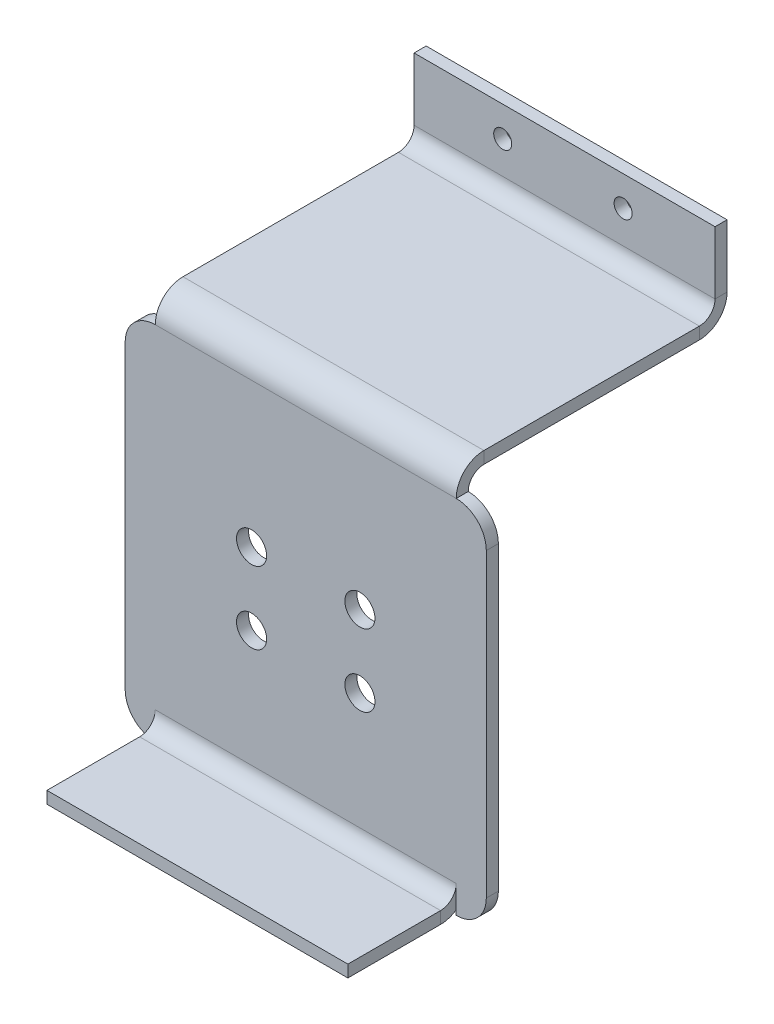
SolidWorks part; units mm, degrees
note: The reader was unsure of these and kept them because the rebuilt part matched: flange length of "Edge-Flange1", "Edge-Flange2", "Edge-Flange3".
material "Alumina"
ref_plane "Front Plane" through (0, 0, 0) normal (0, 0, 1) x (1, 0, 0)
ref_plane "Top Plane" through (0, 0, 0) normal (0, 1, 0) x (1, 0, 0)
ref_plane "Right Plane" through (0, 0, 0) normal (1, 0, 0) x (0, 0, -1)
sketch "Sketch1" plane through (0, 0, 0) normal (0, 0, 1) x (1, 0, 0)
  line L0 (25.2729, 31.228) -> (-24.7271, 31.228)
  line L1 (-29.7271, 26.228) -> (-29.7271, -23.772)
  line L2 (-24.7271, -28.772) -> (25.2729, -28.772)
  line L3 (30.2729, -23.772) -> (30.2729, 26.228)
  arc A0 (-24.7271, 31.228) -> (-29.7271, 26.228) centre (-24.7271, 26.228) ccw
  arc A1 (-29.7271, -23.772) -> (-24.7271, -28.772) centre (-24.7271, -23.772) ccw
  arc A2 (25.2729, -28.772) -> (30.2729, -23.772) centre (25.2729, -23.772) ccw
  arc A3 (30.2729, 26.228) -> (25.2729, 31.228) centre (25.2729, 26.228) ccw
  arc A13 (11.7728, -4.772) -> (9.2729, -2.2721) centre (9.2729, -4.772) ccw
  arc A14 (-8.7271, -2.2721) -> (-11.227, -4.772) centre (-8.7271, -4.772) ccw
  arc A15 (-11.227, -4.772) -> (-6.2272, -4.772) centre (-8.7271, -4.772) ccw
  arc A16 (-6.2272, -4.772) -> (-8.7271, -2.2721) centre (-8.7271, -4.772) ccw
  arc A17 (9.2729, -2.2721) -> (6.773, -4.772) centre (9.2729, -4.772) ccw
  arc A18 (6.773, -4.772) -> (11.7728, -4.772) centre (9.2729, -4.772) ccw
  arc A19 (6.773, 7.228) -> (11.7728, 7.228) centre (9.2729, 7.228) ccw
  arc A20 (9.2729, 9.7279) -> (6.773, 7.228) centre (9.2729, 7.228) ccw
  arc A21 (11.7728, 7.228) -> (9.2729, 9.7279) centre (9.2729, 7.228) ccw
  arc A22 (-8.7271, 9.7279) -> (-11.227, 7.228) centre (-8.7271, 7.228) ccw
  arc A23 (-6.2272, 7.228) -> (-8.7271, 9.7279) centre (-8.7271, 7.228) ccw
  arc A24 (-11.227, 7.228) -> (-6.2272, 7.228) centre (-8.7271, 7.228) ccw
  dimension "D1" = 5
  dimension "D2" = 9.2729
  dimension "D3" = 2.4999
  dimension "D8" = 8.7271
  dimension "D4" = 9.7279
  dimension "D5" = 31.228
  dimension "D6" = 2.2721
  dimension "D7" = 28.772
  dimension "D11" = 25.2729
base flange "Base-Flange2" sketch "Sketch1" thickness 2 reverse thickness direction no parameters "D1"=2.6
edge flange "Edge-Flange1" sketch "Sketch14" flange angle 90 flange length 45 flange position bend outside bend radius 2.6 thickness 2 parameters "D6"=10
sketch "Sketch14" plane through (0, 31.228, -2) normal (0, 1, 0) x (1, 0, 0)
  line L0 (25.2729, 0) -> (-24.7271, 0) construction
  line L1 (25.2729, 0) -> (-24.7271, 0)
  line L2 (-24.7271, 0) -> (-24.7271, 43)
  line L3 (-24.7271, 43) -> (25.2729, 43)
  line L4 (25.2729, 43) -> (25.2729, 0)
bend "EdgeBend1" bend radius 2.6 bend angle 90 parameters "D5"=1
edge flange "Edge-Flange2" sketch "Sketch17" flange angle 90 flange length 15 flange position material inside bend radius 2.6 thickness 2 parameters "D6"=10
sketch "Sketch17" plane through (0, 35.828, -45) normal (0, 0, -1) x (-1, 0, 0)
  line L0 (-25.2729, 0) -> (24.7271, 0) construction
  line L1 (-25.2729, 0) -> (24.7271, 0)
  line L2 (-25.2729, 0) -> (-25.2729, 13)
  line L3 (-25.2729, 13) -> (24.7271, 13)
  line L4 (24.7271, 13) -> (24.7271, 0)
bend "EdgeBend2" bend radius 2.6 bend angle 90 parameters "D5"=2
sketch "Sketch18" plane through (0, 0, -45) normal (0, 0, -1) x (-1, 0, 0)
  line L0 (0, -2.5637) -> (0, 58.1921) construction
  line L1 (24.7271, 48.828) -> (-25.2729, 48.828) construction
  circle A0 centre (-10, 43.828) radius 1.5
  circle A1 centre (10, 43.828) radius 1.5
  dimension "D4" = 3
  dimension "D1" = 10
  dimension "D2" = 10
  dimension "D3" = 5
extrude "Cut-Extrude1" cut sketch "Sketch18" against normal blind 10
edge flange "Edge-Flange3" sketch "Sketch21" flange angle 90 flange length 20 flange position material inside bend radius 2.6 thickness 2 parameters "D6"=10
sketch "Sketch21" plane through (0, -28.772, 0) normal (0, -1, 0) x (1, 0, 0)
  line L2 (-24.7271, 0) -> (-24.7271, 18)
  line L3 (-24.7271, 18) -> (25.2729, 18)
  line L4 (25.2729, 18) -> (25.2729, 0)
  line L7 (-24.7271, 0) -> (25.2729, 0) construction
  line L8 (-24.7271, 0) -> (25.2729, 0)
bend "EdgeBend3" bend radius 2.6 bend angle 90 parameters "D5"=3
sketch "Bend-Lines3" [suppressed] plane through (0, 0, 0) normal (0, 1, 0) x (1, 0, 0)
sketch "Bounding-Box3" [suppressed] plane through (0, 0, 0) normal (0, 1, 0) x (1, 0, 0)
sheet metal parameters "Sheet-Metal2" thickness 2 parameters "D1"=2.6
flat pattern "Flat-Pattern2" [suppressed]
sketch "Bend-Lines4" plane through (0, 0, 0) normal (0, 1, 0) x (1, 0, 0)
sketch3d "Bounding-Box4" [suppressed]
  line L0 (-5, -55, 0) -> (-5, 5, 0) construction
  line L1 (55, -55, 0) -> (55, 5, 0) construction
  line L2 (-5, -55, 0) -> (55, -55, 0) construction
  line L3 (-5, 5, 0) -> (55, 5, 0) construction
sheet metal parameters "Sheet-Metal3" thickness 2 parameters "D1"=2.6
flat pattern "Flat-Pattern2"
sketch "Bend-Lines4" plane through (0, 0, 0) normal (0, 0, 1) x (1, 0, 0)
  line L0 (25.2729, 34.0554) -> (-24.7271, 34.0554) construction
  line L1 (25.2729, 34.0554) -> (-24.7271, 34.0554) construction
sketch3d "Bounding-Box4" [suppressed]
  line L0 (5, -55, 0) -> (5, 51.0549, 0) construction
  line L1 (-55, -55, 0) -> (-55, 51.0549, 0) construction
  line L2 (5, -55, 0) -> (-55, -55, 0) construction
  line L3 (5, 51.0549, 0) -> (-55, 51.0549, 0) construction
bend of the flat pattern "Flatten-<EdgeBend1>1"
sheet metal parameters "Sheet-Metal4" thickness 2 parameters "D1"=2.6
flat pattern "Flat-Pattern2"
sketch "Bend-Lines4" plane through (0, 0, 0) normal (0, 0, 1) x (1, 0, 0)
  line L0 (25.2729, 34.0554) -> (-24.7271, 34.0554) construction
  line L1 (25.2729, 34.0554) -> (-24.7271, 34.0554) construction
  line L2 (25.2729, 75.5103) -> (-24.7271, 75.5103) construction
  line L3 (25.2729, 75.5103) -> (-24.7271, 75.5103) construction
sketch3d "Bounding-Box4" [suppressed]
  line L0 (5, -55, 0) -> (5, 62.5097, 0) construction
  line L1 (-55, -55, 0) -> (-55, 62.5097, 0) construction
  line L2 (5, -55, 0) -> (-55, -55, 0) construction
  line L3 (5, 62.5097, 0) -> (-55, 62.5097, 0) construction
bend of the flat pattern "Flatten-<EdgeBend1>1"
bend of the flat pattern "Flatten-<EdgeBend2>1"
sheet metal parameters "Sheet-Metal5" thickness 2 parameters "D1"=2.6
flat pattern "Flat-Pattern2"
sketch "Bend-Lines4" plane through (0, 0, 0) normal (0, 0, 1) x (1, 0, 0)
  line L0 (25.2729, 34.0554) -> (-24.7271, 34.0554) construction
  line L1 (25.2729, 34.0554) -> (-24.7271, 34.0554) construction
  line L2 (25.2729, 75.5103) -> (-24.7271, 75.5103) construction
  line L3 (25.2729, 75.5103) -> (-24.7271, 75.5103) construction
sketch3d "Bounding-Box4" [suppressed]
  line L0 (5, -55, 0) -> (5, 62.5097, 0) construction
  line L1 (-55, -55, 0) -> (-55, 62.5097, 0) construction
  line L2 (5, -55, 0) -> (-55, -55, 0) construction
  line L3 (5, 62.5097, 0) -> (-55, 62.5097, 0) construction
bend of the flat pattern "Flatten-<EdgeBend1>1"
bend of the flat pattern "Flatten-<EdgeBend2>1"
sheet metal parameters "Sheet-Metal6" thickness 2 parameters "D1"=2.6
flat pattern "Flat-Pattern2"
sketch "Bend-Lines4" plane through (0, 0, 0) normal (0, 0, 1) x (1, 0, 0)
  line L0 (25.2729, 34.0554) -> (-24.7271, 34.0554) construction
  line L1 (25.2729, 34.0554) -> (-24.7271, 34.0554) construction
  line L2 (25.2729, 75.5103) -> (-24.7271, 75.5103) construction
  line L3 (25.2729, 75.5103) -> (-24.7271, 75.5103) construction
  line L4 (25.2729, -26.9994) -> (-24.7271, -26.9994) construction
  line L5 (25.2729, -26.9994) -> (-24.7271, -26.9994) construction
sketch3d "Bounding-Box4" [suppressed]
  line L0 (5, -71.4549, 0) -> (5, 62.5097, 0) construction
  line L1 (-55, -71.4549, 0) -> (-55, 62.5097, 0) construction
  line L2 (5, -71.4549, 0) -> (-55, -71.4549, 0) construction
  line L3 (5, 62.5097, 0) -> (-55, 62.5097, 0) construction
bend of the flat pattern "Flatten-<EdgeBend1>1"
bend of the flat pattern "Flatten-<EdgeBend2>1"
bend of the flat pattern "Flatten-<EdgeBend3>1"
